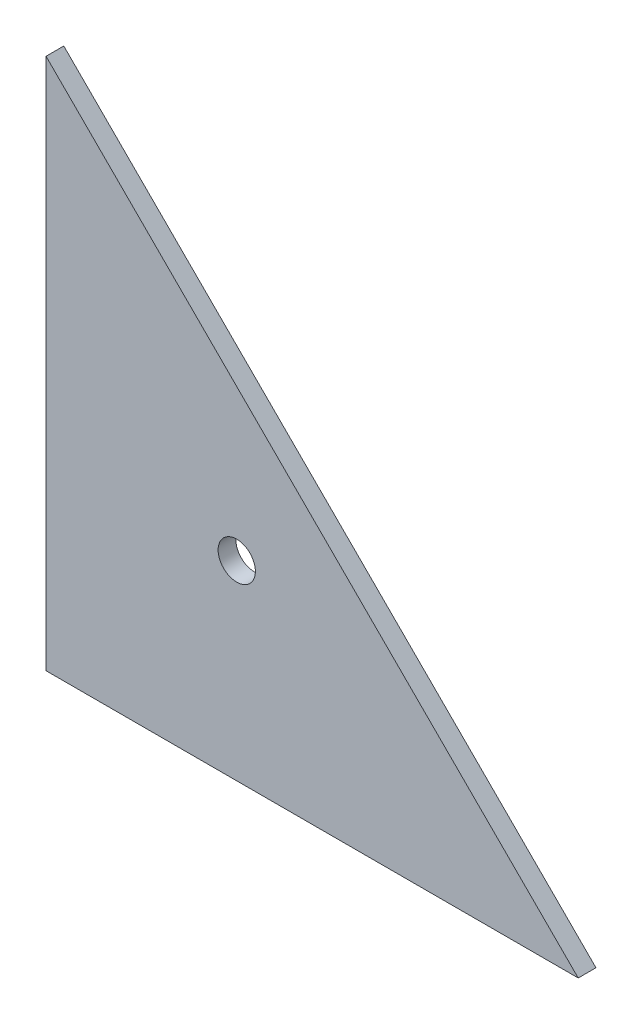
SolidWorks part; units mm, degrees
material "冷轧钢板"
ref_plane "前视基准面" through (0, 0, 0) normal (0, 0, 1) x (1, 0, 0)
ref_plane "上视基准面" through (0, 0, 0) normal (0, 1, 0) x (1, 0, 0)
ref_plane "右视基准面" through (0, 0, 0) normal (1, 0, 0) x (0, 0, -1)
sketch "草图1" plane through (0, 0, 0) normal (0, 0, 1) x (1, 0, 0)
  line L0 (0, 0) -> (0, 60)
  line L1 (0, 60) -> (60, 0)
  line L2 (60, 0) -> (0, 0)
  circle A0 centre (21.5, 21.5) radius 2.1
  dimension "D5" = 4.2
  dimension "D1" = 60
  dimension "D2" = 60
  dimension "D3" = 21.5
  dimension "D4" = 21.5
base flange "基体-法兰1" sketch "草图1" thickness 2 reverse thickness direction no parameters "D1"=0.1
sketch "折弯-线1" [suppressed] plane through (0, 0, 0) normal (0, 1, 0) x (1, 0, 0)
sketch "边界框1" [suppressed] plane through (0, 0, 0) normal (0, 1, 0) x (1, 0, 0)
sheet metal parameters "钣金6" thickness 2 parameters "D1"=0.1
flat pattern "平板型式6" [suppressed]
sketch "折弯-线2" plane through (0, 0, 0) normal (0, 1, 0) x (1, 0, 0)
sketch3d "边界框2" [suppressed]
  line L0 (60, 60, 0) -> (60, 0, 0) construction
  line L1 (0, 60, 0) -> (0, 0, 0) construction
  line L2 (60, 60, 0) -> (0, 60, 0) construction
  line L3 (60, 0, 0) -> (0, 0, 0) construction
